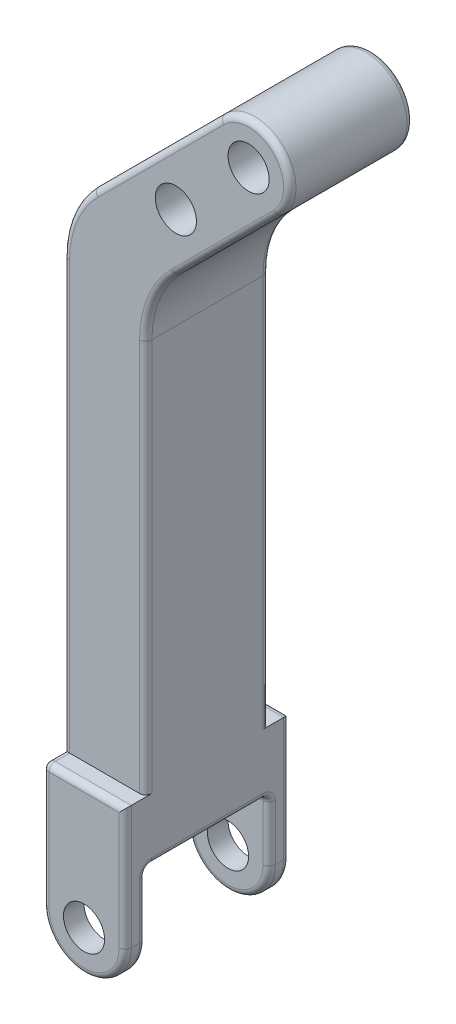
SolidWorks part; units mm, degrees
material "Thornel Mat VMA"
ref_plane "前视基准面" through (0, 0, 0) normal (0, 0, 1) x (1, 0, 0)
ref_plane "上视基准面" through (0, 0, 0) normal (0, 1, 0) x (1, 0, 0)
ref_plane "右视基准面" through (0, 0, 0) normal (1, 0, 0) x (0, 0, -1)
other "Configuration Table"
sketch "草图1" plane through (0, 0, 0) normal (0, 0, 1) x (1, 0, 0)
  circle A0 centre (0, 0) radius 20
  circle A1 centre (0, 0) radius 10
  dimension "D1" = 40
  dimension "D2" = 20
extrude "凸台-拉伸1" add sketch "草图1" along normal blind 60 contours A1 | A0 region at (0, 0, 0)
ref_plane "基准面1" through (0, 0, 30) normal (0, 0, 1) x (1, 0, 0)
sketch "草图2" plane through (0, 0, 30) normal (0, 0, 1) x (1, 0, 0)
  line L0 (0, 0) -> (-70, -70) construction
  line L1 (-70, -70) -> (-70, -320) construction
  line L2 (0, -57.3148) -> (0, 49.9409) construction
  line L3 (-56.8582, 0) -> (46.4003, 0) construction
  line L4 (-14.1421, 14.1421) -> (-90, -61.7157)
  line L5 (14.1421, -14.1421) -> (-50, -78.2843)
  line L6 (-90, -61.7157) -> (-90, -320)
  line L7 (-50, -78.2843) -> (-50, -320)
  line L8 (-90, -320) -> (-50, -320)
  circle A2 centre (0, 0) radius 20 construction
  arc A3 (-14.1421, 14.1421) -> (14.1421, -14.1421) centre (0, 0) ccw
  dimension "D1" = 45
  dimension "D2" = 250
  dimension "D3" = 70
  dimension "D4" = 40
  dimension "D5" = 40
extrude "凸台-拉伸2" add sketch "草图2" along normal mid plane 60 contours L7 L8 L6 L4 A3 L5
sketch "草图4" plane through (0, 0, 60) normal (0, 0, 1) x (1, 0, 0)
  line L0 (-90, -61.7157) -> (-90, -320) construction
  line L1 (-90, -290) -> (-50, -290)
  line L2 (-90, -290) -> (-90, -350)
  line L4 (-50, -290) -> (-50, -350)
  line L5 (-50, -78.2843) -> (-50, -320) construction
  line L6 (-90, -320) -> (-50, -320) construction
  arc A0 (-90, -350) -> (-50, -350) centre (-70, -350) ccw
  circle A1 centre (-70, -350) radius 10
  dimension "D3" = 20
  dimension "D1" = 30
  dimension "D2" = 30
extrude "凸台-拉伸3" add sketch "草图4" along normal blind 10
mirror "镜向1" about plane through (0, 0, 30) normal (0, 0, 1) of "凸台-拉伸3"
sketch "草图5" plane through (0, 0, 0) normal (0, 1, 0) x (1, 0, 0)
  line L0 (0, 0) -> (0, -78.0582) construction
ref_plane "基准面2" through (-70, 0, 0) normal (-1, 0, 0) x (0, 0, 1)
sketch "草图7" plane through (-70, 0, 0) normal (-1, 0, 0) x (0, 0, 1)
  line L0 (-34.1239, -350) -> (109.535, -350) construction
sketch "草图8" plane through (0, 0, 60) normal (0, 0, 1) x (1, 0, 0)
  line L0 (0, 0) -> (-70, -70) construction
  circle A0 centre (-35.3553, -35.3553) radius 10
  dimension "D1" = 20
  dimension "D2" = 50
extrude "切除-拉伸1" cut sketch "草图8" against normal blind 100
fillet "圆角1" radius 50 2 edges at (-90, -61.7157, 30) (-50, -78.2843, 30)
fillet "圆角2" radius 3 34 edges at (-50, -320, 70) (-70, -370, 70) (-50, -335, 60) (-70, -370, 60) (-50, -335, 0) (-70, -370, 0) (-50, -320, -10) (-70, -370, -10) (-70, -320, 60) (-50, -320, 30) (-70, -320, 0) (-90, -290, 65) (-90, -320, 70) (-90, -335, 60) (-90, -320, 30) (-90, -335, 0) (-90, -320, -10) (-90, -290, -5) (-50, -194.4975, 0) (-46.194, -79.8608, 0) (-10.6066, -38.8909, 0) (14.1421, 14.1421, 0) (-44.7487, -16.4645, 0) (-86.194, -63.2922, 0) (-90, -186.2132, 0) (14.1421, 14.1421, 60) (-10.6066, -38.8909, 60) (-46.194, -79.8608, 60) (-50, -194.4975, 60) (-90, -186.2132, 60) (-86.194, -63.2922, 60) (-44.7487, -16.4645, 60) (-70, -290, 70) (-70, -290, -10)
